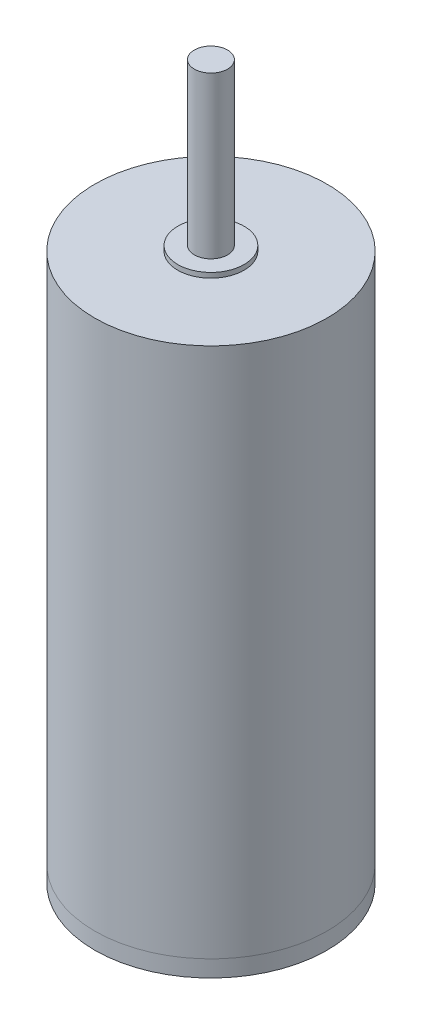
SolidWorks part; units mm, degrees
ref_plane "Front Plane" through (0, 0, 0) normal (0, 0, 1) x (1, 0, 0)
ref_plane "Top Plane" through (0, 0, 0) normal (0, 1, 0) x (1, 0, 0)
ref_plane "Right Plane" through (0, 0, 0) normal (1, 0, 0) x (0, 0, -1)
sketch "Sketch1" plane through (0, 0, 0) normal (0, 1, 0) x (1, 0, 0)
  circle A0 centre (0, 0) radius 3.5
  dimension "D1" = 7
extrude "Boss-Extrude1" add sketch "Sketch1" along normal blind 16
sketch "Sketch2" plane through (0, 16, 0) normal (0, 1, 0) x (1, 0, 0)
  circle A0 centre (0, 0) radius 0.5
  dimension "D1" = 1
extrude "Boss-Extrude2" add sketch "Sketch2" along normal blind 5
sketch "Sketch3" plane through (0, 16, 0) normal (0, 1, 0) x (1, 0, 0)
  circle A0 centre (0, 0) radius 1
  dimension "D1" = 2
extrude "Boss-Extrude3" add sketch "Sketch3" along normal blind 0.15
extrude "Boss-Extrude4" add sketch "Sketch1<2>" against normal blind 0.5 separate body
sketch "Sketch1<2>" plane through (0, 0, 0) normal (0, 1, 0) x (1, 0, 0) same geometry as "Sketch1"
